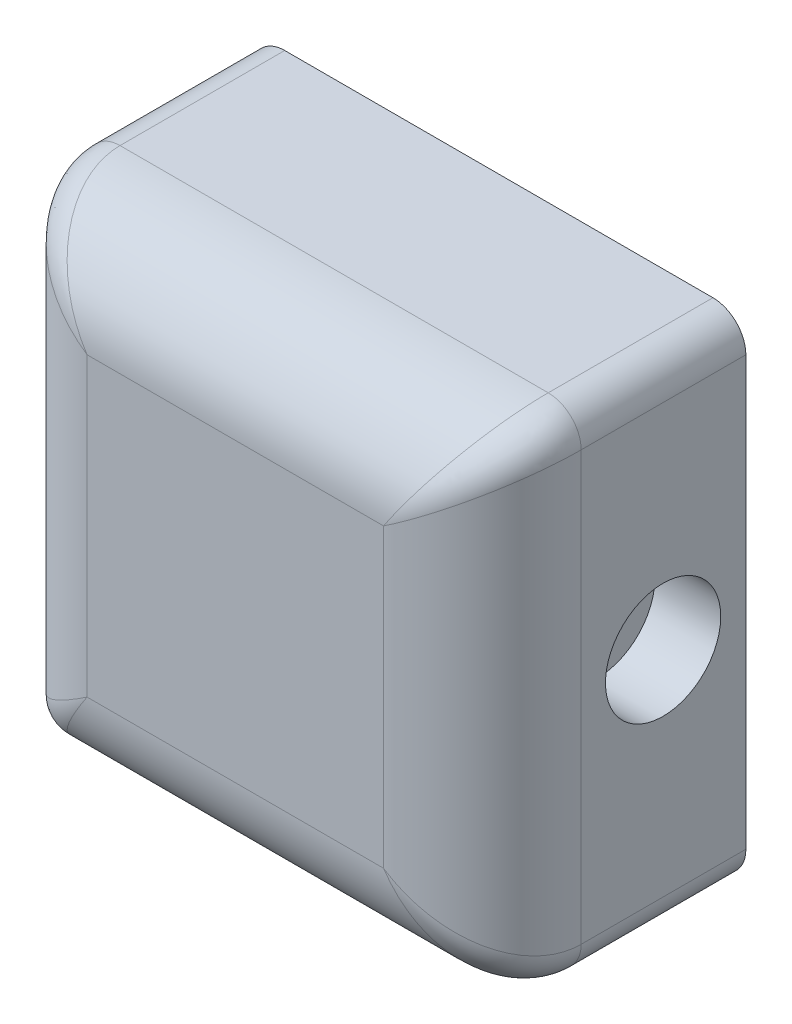
SolidWorks part; units mm, degrees
ref_plane "Front Plane" through (0, 0, 0) normal (0, 0, 1) x (1, 0, 0)
ref_plane "Top Plane" through (0, 0, 0) normal (0, 1, 0) x (1, 0, 0)
ref_plane "Right Plane" through (0, 0, 0) normal (1, 0, 0) x (0, 0, -1)
sketch "Base Sketch" plane through (0, 0, 0) normal (0, 0, 1) x (1, 0, 0)
  line L1 (-7.5, 7.5) -> (7.5, 7.5)
  line L2 (-7.5, 7.5) -> (-7.5, -7.5)
  line L3 (-7.5, -7.5) -> (7.5, -7.5)
  line L4 (7.5, 7.5) -> (7.5, -7.5)
  line L5 (-7.5, 7.5) -> (7.5, -7.5) construction
  line L6 (-7.5, -7.5) -> (7.5, 7.5) construction
  point P0 (0, 0)
  dimension "D1" = 15
  dimension "D2" = 15
extrude "Base Sketch Extrude" add sketch "Base Sketch" along normal blind 8
shell "Tip Cap Shell" thickness 3 removed face at (0, 0, 0)
fillet "Fillet1" radius 3 4 edges at (0, -7.5, 8) (-7.5, 0, 8) (0, 7.5, 8) (7.5, 0, 8)
fillet "Fillet2" radius 1 8 edges at (6.6213, 6.6213, 7.1213) (6.6213, -6.6213, 7.1213) (-6.6213, -6.6213, 7.1213) (-6.6213, 6.6213, 7.1213) (7.5, 7.5, 2.5) (7.5, -7.5, 2.5) (-7.5, -7.5, 2.5) (-7.5, 7.5, 2.5)
fillet "Fillet3" radius 2 4 edges at (4.5, -4.5, 2.5) (4.5, 4.5, 2.5) (-4.5, -4.5, 2.5) (-4.5, 4.5, 2.5)
sketch "Sketch2" plane through (7.5, 0, 0) normal (1, 0, 0) x (0, 0, -1)
  line L0 (-8, 0) -> (0, 0) construction
  line L1 (-8, -4.5) -> (-8, 4.5) construction
  circle A0 centre (-2.5126, 0) radius 1.75
  dimension "D1" = 3.5
extrude "Top section connection hole Cut" cut sketch "Sketch2" against normal blind 2
mirror "Mirror1" about plane through (0, 0, 0) normal (1, 0, 0) of "Top section connection hole Cut"
